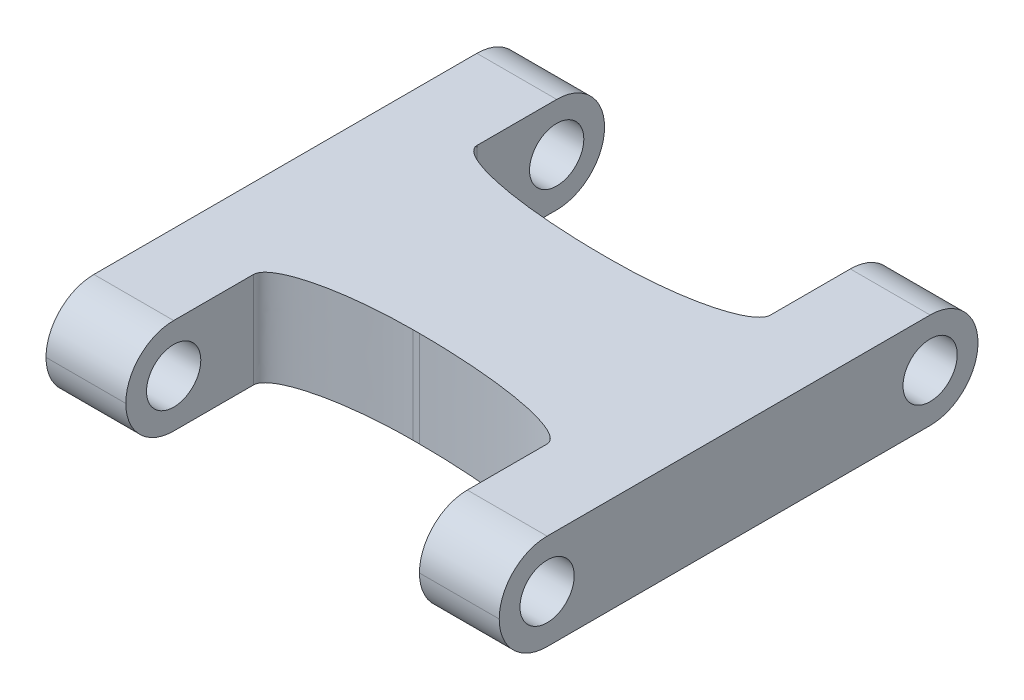
SolidWorks part; units mm, degrees
ref_plane "Front Plane" through (0, 0, 0) normal (0, 0, 1) x (1, 0, 0)
ref_plane "Top Plane" through (0, 0, 0) normal (0, 1, 0) x (1, 0, 0)
ref_plane "Right Plane" through (0, 0, 0) normal (1, 0, 0) x (0, 0, -1)
sketch "Sketch1" plane through (0, 0, 0) normal (0, 1, 0) x (1, 0, 0)
  line L0 (0, 0) -> (0, 30)
  line L1 (0, 30) -> (5, 30)
  line L2 (5, 30) -> (5, 20)
  line L3 (5, 20) -> (23.4, 20)
  line L4 (23.4, 20) -> (23.4, 30)
  line L5 (23.4, 30) -> (28.4, 30)
  line L6 (28.4, 30) -> (28.4, 0)
  line L7 (28.4, 0) -> (23.4, 0)
  line L8 (23.4, 0) -> (23.4, 10)
  line L9 (23.4, 10) -> (5, 10)
  line L10 (5, 10) -> (5, 0)
  line L11 (5, 0) -> (0, 0)
  dimension "D1" = 18.4
  dimension "D2" = 30
  dimension "D3" = 10
  dimension "D4" = 5
extrude "Boss-Extrude1" add sketch "Sketch1" along normal blind 6
fillet "Fillet1" radius 3 8 edges at (2.5, 0, -30) (2.5, 6, -30) (25.9, 0, -30) (25.9, 6, -30) (2.5, 0, 0) (2.5, 6, 0) (25.9, 0, 0) (25.9, 6, 0)
sketch "Sketch2" plane through (28.4, 0, 0) normal (1, 0, 0) x (0, 0, -1)
  line L0 (3, 3) -> (27, 3) construction
  circle A0 centre (3, 3) radius 1.7
  circle A1 centre (27, 3) radius 1.7
  arc A2 (30, 3) -> (27, 6) centre (27, 3) ccw construction
  arc A3 (3, 6) -> (0, 3) centre (3, 3) ccw construction
  dimension "D1" = 3.4
extrude "Cut-Extrude1" cut sketch "Sketch2" against normal through all
fillet "Fillet2" radius 2 2 edges at (23.4, 3, -20) (5, 3, -10) second distance 8 first distance on face at (23.4, 3, -28.7) first distance on face at (5, 3, -1.3)
fillet "Fillet3" radius 10 2 edges at (5, 3, -20) (23.4, 3, -10) second distance 2 first distance on face at (12.8, 3.75, -20) first distance on face at (15.6, 3.75, -10)
